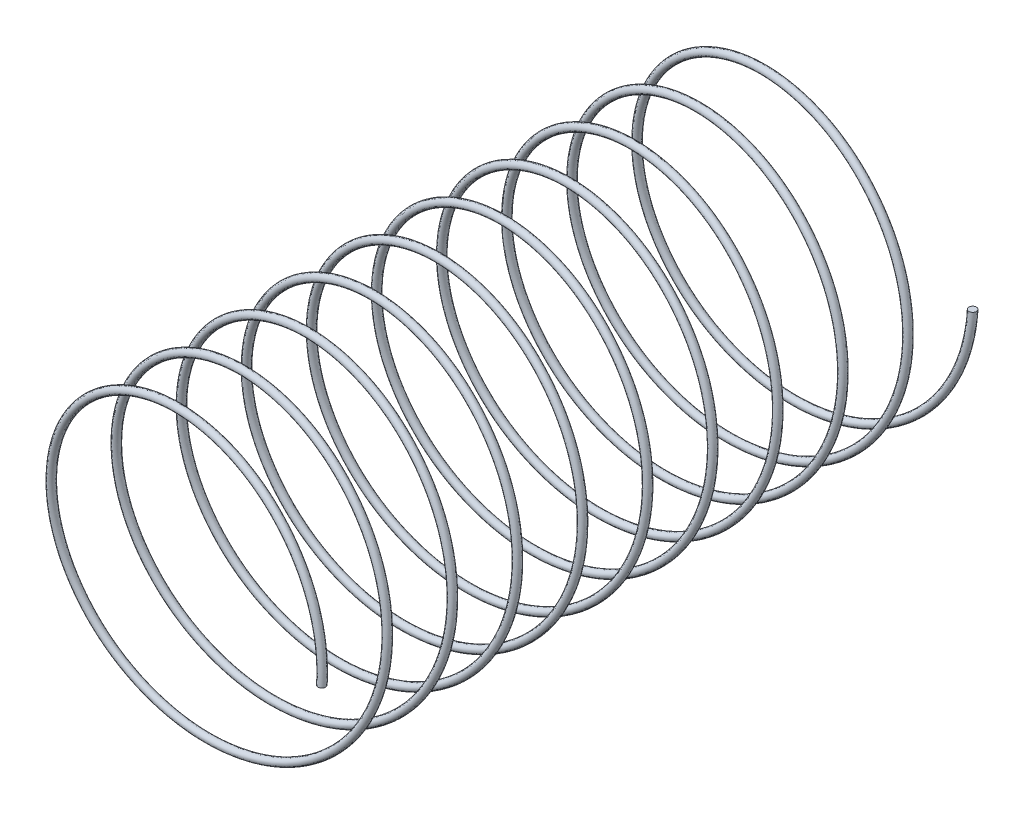
SolidWorks part; units mm, degrees
material "Alloy Steel"
ref_plane "Front Plane" through (0, 0, 0) normal (0, 0, 1) x (1, 0, 0)
ref_plane "Top Plane" through (0, 0, 0) normal (0, 1, 0) x (1, 0, 0)
ref_plane "Right Plane" through (0, 0, 0) normal (1, 0, 0) x (0, 0, -1)
sketch "Sketch1" plane through (0, 0, 0) normal (0, 0, 1) x (1, 0, 0)
  circle A0 centre (0, 0) radius 5.08
curve "Helix/Spiral4" pitch 2.1844 height 21.844 turns 10
sketch "Sketch2" plane through (0, 0, 0) normal (0, 1, 0) x (1, 0, 0)
  circle A0 centre (5.08, 0) radius 0.127
  point P2 (0, 0)
  point P3 (0, 0)
  point P4 (0, 0)
  point P5 (0, 0)
  point P6 (0, 0)
  point P7 (0, 0)
  point P8 (0, 0)
  point P9 (0, 0)
  point P10 (0, 0)
  point P11 (0, 0)
  point P12 (0, 0)
  point P13 (0, 0)
sweep "Sweep1" add profiles "Sketch2" path "Helix/Spiral4"
